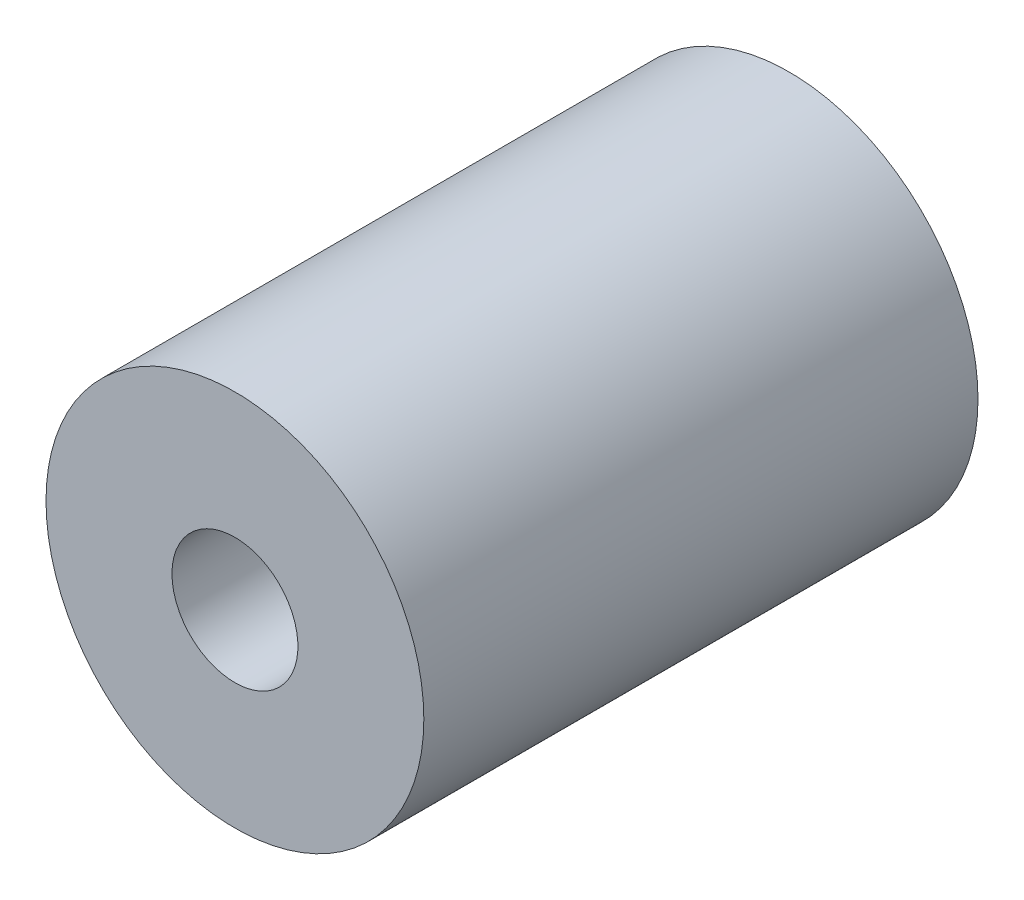
SolidWorks part; units mm, degrees
ref_plane "Front Plane" through (0, 0, 0) normal (0, 0, 1) x (1, 0, 0)
ref_plane "Top Plane" through (0, 0, 0) normal (0, 1, 0) x (1, 0, 0)
ref_plane "Right Plane" through (0, 0, 0) normal (1, 0, 0) x (0, 0, -1)
sketch "Sketch1" plane through (0, 0, 0) normal (0, 0, 1) x (1, 0, 0)
  circle A0 centre (0, 0) radius 7.5
extrude "Boss-Extrude1" add sketch "Sketch1" against normal up to surface (22 mm away)
sketch "Sketch2" plane through (0, 0, 0) normal (0, 0, 1) x (1, 0, 0)
  circle A0 centre (0, 0) radius 10
sketch "Sketch9" plane through (0, 0, -22) normal (0, 0, -1) x (-1, 0, 0)
  circle A0 centre (0, 0) radius 2.5
extrude "Cut-Extrude1" cut sketch "Sketch9" against normal through all
